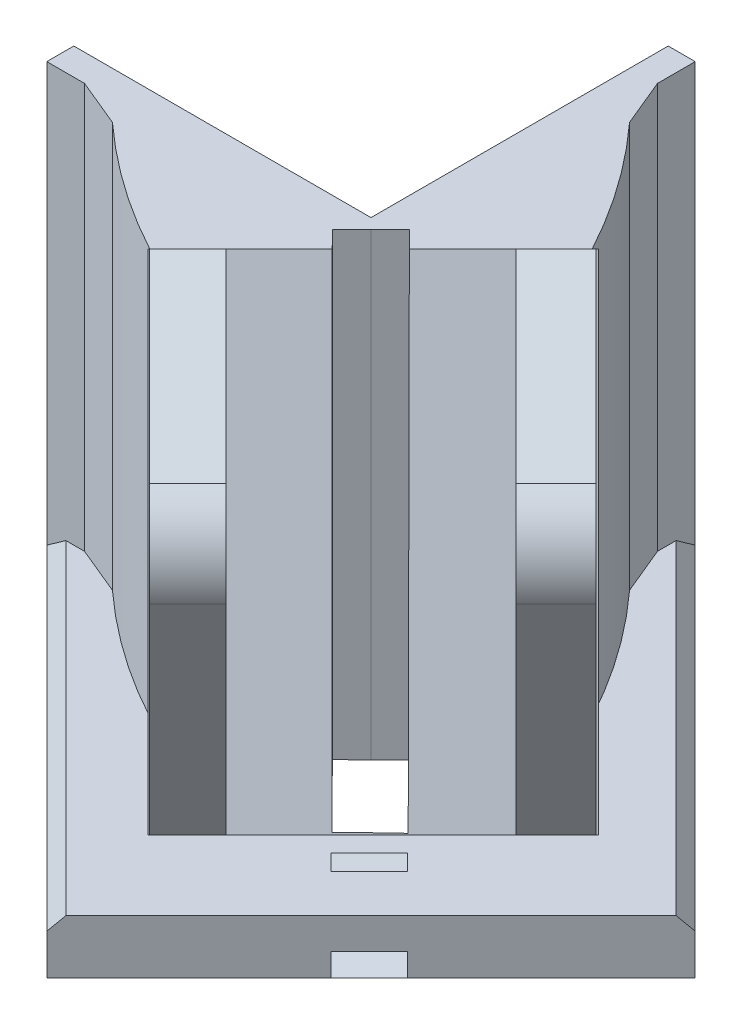
SolidWorks part; units mm, degrees
ref_plane "前视基准面" through (0, 0, 0) normal (0, 0, 1) x (1, 0, 0)
ref_plane "上视基准面" through (0, 0, 0) normal (0, 1, 0) x (1, 0, 0)
ref_plane "右视基准面" through (0, 0, 0) normal (1, 0, 0) x (0, 0, -1)
sketch "草图1" plane through (0, 0, 0) normal (0, 1, 0) x (1, 0, 0)
  line L0 (0, 0) -> (0, 110)
  line L1 (0, 110) -> (10, 110)
  line L2 (10, 110) -> (10, -10)
  line L3 (10, -10) -> (-110, -10)
  line L4 (-110, -10) -> (-110, 0)
  line L5 (-110, 0) -> (0, 0)
  dimension "D1" = 110
  dimension "D2" = 110
  dimension "D3" = 10
  dimension "D4" = 10
extrude "凸台-拉伸1" add sketch "草图1" along normal blind 150
sketch "草图2" plane through (0, 150, 0) normal (0, 1, 0) x (1, 0, 0)
  line L0 (0, 0) -> (65.5114, -65.5114) construction
  line L1 (-86.0377, -10) -> (10, -10)
  line L2 (-110, -10) -> (10, -10) construction
  line L3 (-86.0377, -10) -> (-38.0189, -58.0189)
  line L4 (-38.0189, -58.0189) -> (10, -10)
  line L5 (10, 86.0377) -> (58.0189, 38.0189)
  line L6 (10, -10) -> (58.0189, 38.0189)
  line L7 (10, 86.0377) -> (10, -10)
  line M8 (10, -10) -> (10, 110)
  dimension "D1" = 67.9089
  dimension "D2" = 67.9089
extrude "凸台-拉伸2" add sketch "草图2" against normal blind 150 contours L6 L5 M8 | L1 L3 L4
ref_plane "基准面1" through (-0.2892, 0, 0.2892) normal (-0.7071, 0, 0.7071) x (0.7071, 0, 0.7071)
sketch "草图5" plane through (0, 150, 0) normal (0, 1, 0) x (1, 0, 0)
  line L0 (-86.0377, -10) -> (-38.0189, -58.0189)
  line L1 (-38.0189, -58.0189) -> (-30.9478, -50.9478)
  line L2 (-38.0189, -58.0189) -> (58.0189, 38.0189) construction
  line L6 (10, 86.0377) -> (58.0189, 38.0189)
  line L7 (58.0189, 38.0189) -> (50.9478, 30.9478)
  arc A0 (-86.0377, -10) -> (-30.9478, -50.9478) centre (80.5433, 156.5811) ccw
  arc A2 (10, 86.0377) -> (50.9478, 30.9478) centre (-156.5811, -80.5433) cw
  dimension "D1" = 10
  dimension "D2" = 10
extrude "切除-拉伸3" cut sketch "草图5" against normal blind 161
ref_plane "基准面2" through (-40.9478, 0, 40.9478) normal (-0.7071, 0, 0.7071) x (0.7071, 0, 0.7071)
ref_plane "基准面3" through (40.9478, 0, -40.9478) normal (-0.7071, 0, 0.7071) x (0.7071, 0, 0.7071)
chamfer "倒角4" distance 10 1 edges at (-86.0377, 75, 10)
chamfer "倒角5" distance 10 1 edges at (10, 75, -86.0377)
ref_plane "基准面4" through (0, 0, 0) normal (0, -1, 0) x (-1, 0, 0)
sketch "草图8" plane through (0, 0, 0) normal (0, -1, 0) x (-1, 0, 0)
  line L0 (110, 0) -> (0, 0)
  line L1 (0, 0) -> (0, 110)
  line L2 (0, 110) -> (-10, 110)
  line L3 (-10, 110) -> (-133.7437, -13.7437)
  line L4 (-133.7437, -13.7437) -> (-73.7437, -73.7437)
  line L5 (0, 0) -> (-104.9581, -104.9581)
  line L6 (30.9478, -50.9478) -> (-50.9478, 30.9478) construction
  line L8 (110, 0) -> (110, -10)
  line L9 (110, -10) -> (-13.7437, -133.7437)
  line L10 (-13.7437, -133.7437) -> (-73.7437, -73.7437)
  dimension "D1" = 175
extrude "凸台-拉伸7" add sketch "草图8" along normal blind 20 contours L0 L8 L9 L10 L4 L3 L2 L1
chamfer "倒角6" distance 5 angle 45 1 edges at (-48.1282, 0, 71.8718)
chamfer "倒角7" distance 5 angle 45 1 edges at (71.8718, 0, -48.1282)
sketch "草图9" plane through (-0.2892, 0, 0.2892) normal (-0.7071, 0, 0.7071) x (0.7071, 0, 0.7071)
  line L0 (14.1421, 150) -> (67.7564, 0)
  line L1 (-55, 0) -> (55, 0) construction
  line L2 (67.7564, 0) -> (14.1421, 0)
  line L3 (14.1421, 0) -> (14.1421, 150)
extrude "凸台-拉伸8" add sketch "草图9" along normal blind 58 and the other way blind 60 from offset 0 contours L0 L2 L3
sketch "草图10" plane through (-40.9478, 0, 40.9478) normal (-0.7071, 0, 0.7071) x (0.7071, 0, 0.7071)
  line L0 (14.1421, 150) -> (87.3338, 126.5562)
  line L1 (14.1421, 150) -> (67.7564, 0)
  line L2 (-55, 0) -> (55, 0) construction
  line L3 (14.1421, 150) -> (67.7564, 0) construction
  line L4 (67.7564, 0) -> (98.0115, 95.3957)
  line L5 (40.9493, 75) -> (131.6863, 107.432) construction
  arc A0 (98.0115, 95.3957) -> (87.3338, 126.5562) centre (71.626, 103.7639) ccw
extrude "凸台-拉伸9" add sketch "草图10" against normal blind 20
sketch "草图12" plane through (40.9478, 0, -40.9478) normal (-0.7071, 0, 0.7071) x (0.7071, 0, 0.7071)
  line L0 (14.1421, 150) -> (87.3338, 126.5562)
  line L1 (87.3338, 126.5562) -> (14.1421, 150) construction
  line L2 (14.1421, 150) -> (67.7564, 0)
  line L3 (67.7564, 0) -> (98.0115, 95.3957)
  arc A0 (98.0115, 95.3957) -> (87.3338, 126.5562) centre (71.626, 103.7639) ccw
extrude "凸台-拉伸17" add sketch "草图12" along normal blind 20 and the other way blind 1 from offset 0
sketch "草图13" plane through (-40.9478, 0, 40.9478) normal (-0.7071, 0, 0.7071) x (0.7071, 0, 0.7071)
  circle A0 centre (77.0424, 104.5151) radius 10
  dimension "D1" = 20
extrude "切除-拉伸6" cut sketch "草图13" against normal through all both and the other way through all
sketch "草图15" plane through (-0.2892, 0, 0.2892) normal (-0.7071, 0, 0.7071) x (0.7071, 0, 0.7071)
  line L0 (92.7543, 0) -> (104.2893, -11.535) construction
  line L1 (-65.7107, 0) -> (104.2893, 0) construction
  line L2 (104.2893, -20) -> (104.2893, -5) construction
  line L3 (84.2893, 0) -> (104.2893, -20) construction
  line L4 (75.8243, 0) -> (95.8243, -20) construction
  line L5 (-70.7107, -20) -> (104.2893, -20) construction
  line L6 (75.8243, 0) -> (84.2893, 0)
  line L7 (104.2893, -11.535) -> (104.2893, -20)
  arc A0 (84.2893, 0) -> (104.2893, -11.535) centre (115.7752, 31.4859) ccw
  arc A1 (75.8243, 0) -> (104.2893, -20) centre (147.3102, 71.4859) ccw
extrude "切除-拉伸8" cut sketch "草图15" against normal blind 10 and the other way blind 10 from offset 0
sketch "草图17" plane through (-40.9478, 0, 40.9478) normal (-0.7071, 0, 0.7071) x (0.7071, 0, 0.7071)
  line L0 (67.0424, 104.5151) -> (67.7564, 0) construction
  line L1 (67.7564, 0) -> (98.0115, 95.3957) construction
  line L2 (67.7564, 0) -> (67.7564, -42.8492) construction
  circle A0 centre (77.0424, 104.5151) radius 10 construction
sketch "草图18" plane through (0, -20, 0) normal (0, -1, 0) x (1, 0, 0)
  line L0 (0, 0) -> (73.4545, 74.0328) construction
  line L1 (66.3835, 81.1039) -> (80.5256, 66.9618) construction
  line L2 (6.7607, 88.5796) -> (94.4881, 1.2451) construction
  line L3 (40.4873, 55.004) -> (-3.3805, 10.9388)
  line L4 (-3.3805, 10.9388) -> (3.7803, 3.81)
  line L5 (40.4873, 55.004) -> (47.5743, 47.9488)
  line L6 (54.6848, 40.9175) -> (47.5743, 47.9488)
  line L7 (10.965, -3.2947) -> (3.7803, 3.81)
  line L8 (54.6848, 40.9175) -> (10.965, -3.2947)
  point P13 (-3.3805, 10.9388)
  point P14 (0, 0)
  dimension "D1" = 10
  dimension "D2" = 62.1782
  dimension "D3" = 36.7446
extrude "切除-拉伸9" cut sketch "草图18" against normal blind 182 and the other way blind 31
